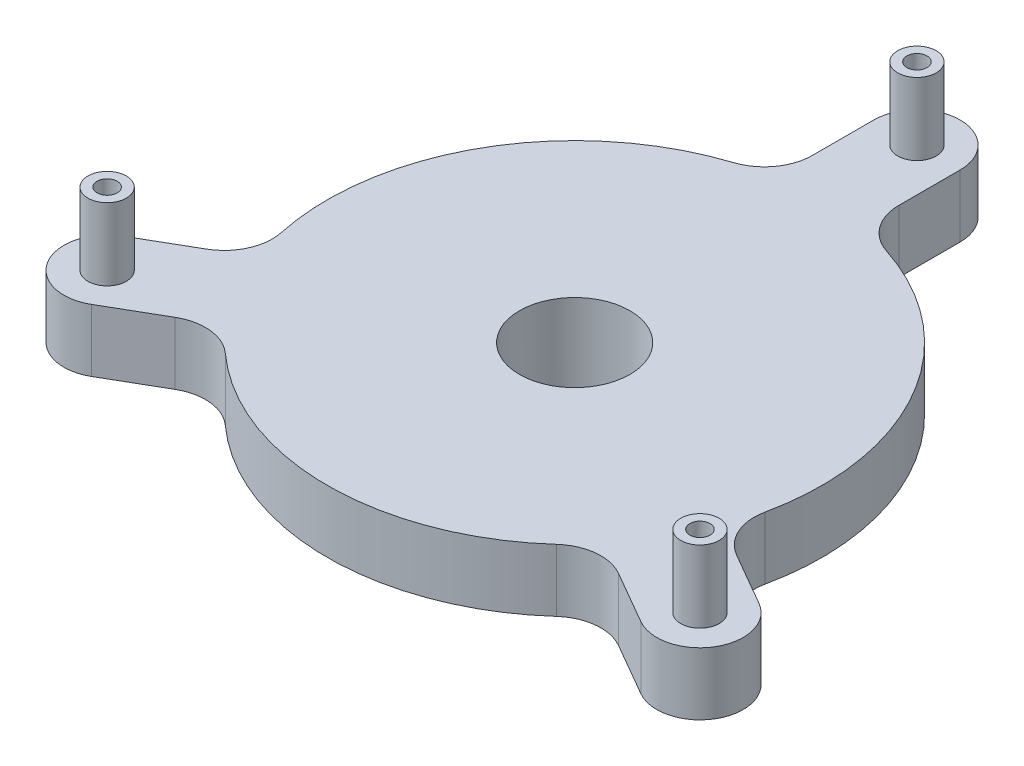
SolidWorks part; units mm, degrees
ref_plane "前基準面" through (0, 0, 0) normal (0, 0, 1) x (1, 0, 0)
ref_plane "上基準面" through (0, 0, 0) normal (0, 1, 0) x (1, 0, 0)
ref_plane "右基準面" through (0, 0, 0) normal (1, 0, 0) x (0, 0, -1)
sketch "草圖1" plane through (0, 0, 0) normal (0, 1, 0) x (1, 0, 0)
  circle A0 centre (0, 0) radius 82.5
  circle A1 centre (0, 0) radius 11.5
  dimension "D1" = 165
  dimension "D2" = 23
extrude "填料-伸長1" add sketch "草圖1" along normal blind 8
sketch "草圖2" plane through (0, 8, 0) normal (0, 1, 0) x (1, 0, 0)
  line L0 (0, 0) -> (0, 82.5) construction
  line L1 (0, 0) -> (71.4471, -41.25) construction
  line L2 (0, 0) -> (-71.4471, -41.25) construction
  circle A0 centre (0, 0) radius 82.5 construction
  circle A1 centre (0, 71.25) radius 4
  circle A2 centre (61.7043, -35.625) radius 4
  circle A3 centre (-61.7043, -35.625) radius 4
  circle A4 centre (0, 71.25) radius 2.1
  circle A5 centre (61.7043, -35.625) radius 2.1
  circle A6 centre (-61.7043, -35.625) radius 2.1
  point P15 (0, 0)
  point P22 (0, 0)
  dimension "D1" = 8
  dimension "D6" = 4.2
  dimension "D2" = 3
  dimension "D3" = 71.25
  dimension "D4" = 1.9
  dimension "D5" = 3
extrude "填料-伸長2" add sketch "草圖2" along normal blind 15
sketch "草圖3" plane through (0, 0, 0) normal (0, -1, 0) x (1, 0, 0)
  circle A0 centre (0, 0) radius 11.5 construction
  circle A1 centre (0, 0) radius 11.5
  circle A2 centre (0, 0) radius 34
  dimension "D2" = 68
  dimension "D1" = 22.5
extrude "填料-伸長3" add sketch "草圖3" along normal blind 5
sketch "草圖4" plane through (0, 8, 0) normal (0, 1, 0) x (1, 0, 0)
  line L0 (-9, 71.25) -> (-9, 58.4915)
  line L1 (9, 71.25) -> (9, 58.4915)
  line L2 (66.2043, -27.8308) -> (55.1551, -21.4515)
  line L3 (57.2043, -43.4192) -> (46.1551, -37.04)
  line L4 (-57.2043, -43.4192) -> (-46.1551, -37.04)
  line L5 (-66.2043, -27.8308) -> (-55.1551, -21.4515)
  circle A0 centre (0, 0) radius 51.5 construction
  arc A1 (-15.9106, 48.9806) -> (-50.3738, -10.7114) centre (0, 0) ccw
  circle A2 centre (-61.7043, -35.625) radius 9
  arc A3 (-66.2043, -27.8308) -> (-57.2043, -43.4192) centre (-61.7043, -35.625) ccw
  arc A4 (50.3738, -10.7114) -> (15.9106, 48.9806) centre (0, 0) ccw
  arc A5 (-46.1551, -37.04) -> (-34.4632, -38.2693) centre (-41.1551, -45.7002) cw
  arc A6 (46.1551, -37.04) -> (34.4632, -38.2693) centre (41.1551, -45.7002) ccw
  arc A7 (55.1551, -21.4515) -> (50.3738, -10.7114) centre (60.1551, -12.7912) cw
  arc A8 (9, 58.4915) -> (15.9106, 48.9806) centre (19, 58.4915) ccw
  arc A9 (-9, 58.4915) -> (-15.9106, 48.9806) centre (-19, 58.4915) cw
  arc A10 (-55.1551, -21.4515) -> (-50.3738, -10.7114) centre (-60.1551, -12.7912) ccw
  circle A11 centre (0, 71.25) radius 9
  arc A12 (9, 71.25) -> (-9, 71.25) centre (0, 71.25) ccw
  circle A13 centre (0, 0) radius 11.5 construction
  circle A14 centre (61.7043, -35.625) radius 9
  arc A15 (57.2043, -43.4192) -> (66.2043, -27.8308) centre (61.7043, -35.625) ccw
  circle A16 centre (0, 0) radius 11.5
  arc A17 (-34.4632, -38.2693) -> (34.4632, -38.2693) centre (0, 0) ccw
  circle A18 centre (0, 0) radius 82.5 construction
  circle A19 centre (0, 0) radius 82.5
  point P28 (0, 0)
  point P35 (-9, 50.7075)
  circle M24 centre (0, 0) radius 82.5
  dimension "D7" = 10
  dimension "D5" = 18
  dimension "D1" = 5
  dimension "D2" = 5
  dimension "D3" = 5
  dimension "D4" = 40
  dimension "D6" = 3
extrude "除料-伸長1" cut sketch "草圖4" against normal blind 10 and the other way through all contours A17 A5 L4 A3 L5 A10 A1 A9 L0 A12 L1 A8 A4 A7 L2 A15 L3 A6 M24 region at (-80.1665, 8, 0)
sketch "草圖5" plane through (0, 0, 0) normal (0, -1, 0) x (1, 0, 0)
  line L6 (-46.1551, 37.04) -> (-57.2043, 43.4192)
  line L7 (-66.2043, 27.8308) -> (-55.1551, 21.4515)
  line L8 (-9, -58.4915) -> (-9, -71.25)
  line L9 (9, -71.25) -> (9, -58.4915)
  line L10 (55.1551, 21.4515) -> (66.2043, 27.8308)
  line L11 (57.2043, 43.4192) -> (46.1551, 37.04)
  line L12 (-46.1551, 37.04) -> (-57.2043, 43.4192)
  line L13 (-66.2043, 27.8308) -> (-55.1551, 21.4515)
  line L14 (-9, -58.4915) -> (-9, -71.25)
  line L15 (9, -71.25) -> (9, -58.4915)
  line L16 (55.1551, 21.4515) -> (66.2043, 27.8308)
  line L17 (57.2043, 43.4192) -> (46.1551, 37.04)
  circle A0 centre (0, 0) radius 46
  arc A13 (34.4632, 38.2693) -> (-34.4632, 38.2693) centre (0, 0) ccw
  arc A14 (-46.1551, 37.04) -> (-34.4632, 38.2693) centre (-41.1551, 45.7002) ccw
  arc A15 (-57.2043, 43.4192) -> (-66.2043, 27.8308) centre (-61.7043, 35.625) ccw
  arc A16 (-50.3738, 10.7114) -> (-55.1551, 21.4515) centre (-60.1551, 12.7912) ccw
  arc A17 (-50.3738, 10.7114) -> (-15.9106, -48.9806) centre (0, 0) ccw
  arc A18 (-9, -58.4915) -> (-15.9106, -48.9806) centre (-19, -58.4915) ccw
  arc A19 (-9, -71.25) -> (9, -71.25) centre (0, -71.25) ccw
  arc A20 (15.9106, -48.9806) -> (9, -58.4915) centre (19, -58.4915) ccw
  arc A21 (15.9106, -48.9806) -> (50.3738, 10.7114) centre (0, 0) ccw
  arc A22 (55.1551, 21.4515) -> (50.3738, 10.7114) centre (60.1551, 12.7912) ccw
  arc A23 (66.2043, 27.8308) -> (57.2043, 43.4192) centre (61.7043, 35.625) ccw
  arc A24 (34.4632, 38.2693) -> (46.1551, 37.04) centre (41.1551, 45.7002) ccw
  arc A25 (34.4632, 38.2693) -> (-34.4632, 38.2693) centre (0, 0) ccw
  arc A26 (-46.1551, 37.04) -> (-34.4632, 38.2693) centre (-41.1551, 45.7002) ccw
  arc A27 (-57.2043, 43.4192) -> (-66.2043, 27.8308) centre (-61.7043, 35.625) ccw
  arc A28 (-50.3738, 10.7114) -> (-55.1551, 21.4515) centre (-60.1551, 12.7912) ccw
  arc A29 (-50.3738, 10.7114) -> (-15.9106, -48.9806) centre (0, 0) ccw
  arc A30 (-9, -58.4915) -> (-15.9106, -48.9806) centre (-19, -58.4915) ccw
  arc A31 (-9, -71.25) -> (9, -71.25) centre (0, -71.25) ccw
  arc A32 (15.9106, -48.9806) -> (9, -58.4915) centre (19, -58.4915) ccw
  arc A33 (15.9106, -48.9806) -> (50.3738, 10.7114) centre (0, 0) ccw
  arc A34 (55.1551, 21.4515) -> (50.3738, 10.7114) centre (60.1551, 12.7912) ccw
  arc A35 (66.2043, 27.8308) -> (57.2043, 43.4192) centre (61.7043, 35.625) ccw
  arc A36 (34.4632, 38.2693) -> (46.1551, 37.04) centre (41.1551, 45.7002) ccw
  dimension "D1" = 0
  dimension "D2" = 92
extrude "填料-伸長4" add sketch "草圖5" along normal up to surface (5 mm away) contours A25 A26 L12 A27 L13 A28 A29 A30 L14 A31 L15 A32 A33 A34 L16 A35 L17 A36 up to face at (0, -5, -34)
sketch "草圖6" plane through (0, 0, 0) normal (0, 1, 0) x (1, 0, 0)
  circle A1 centre (0, 0) radius 11.5
  circle A2 centre (0, 0) radius 11.5
  dimension "D1" = 0
extrude "除料-伸長2" cut sketch "草圖6" against normal through all
sketch "草圖7" plane through (0, -5, 0) normal (0, -1, 0) x (1, 0, 0)
  circle A0 centre (0, 0) radius 34.75
  circle A1 centre (0, 0) radius 11.5 construction
  circle A2 centre (0, 0) radius 11.5
  dimension "D1" = 69.5
extrude "填料-伸長5" add sketch "草圖7" along normal blind 5
